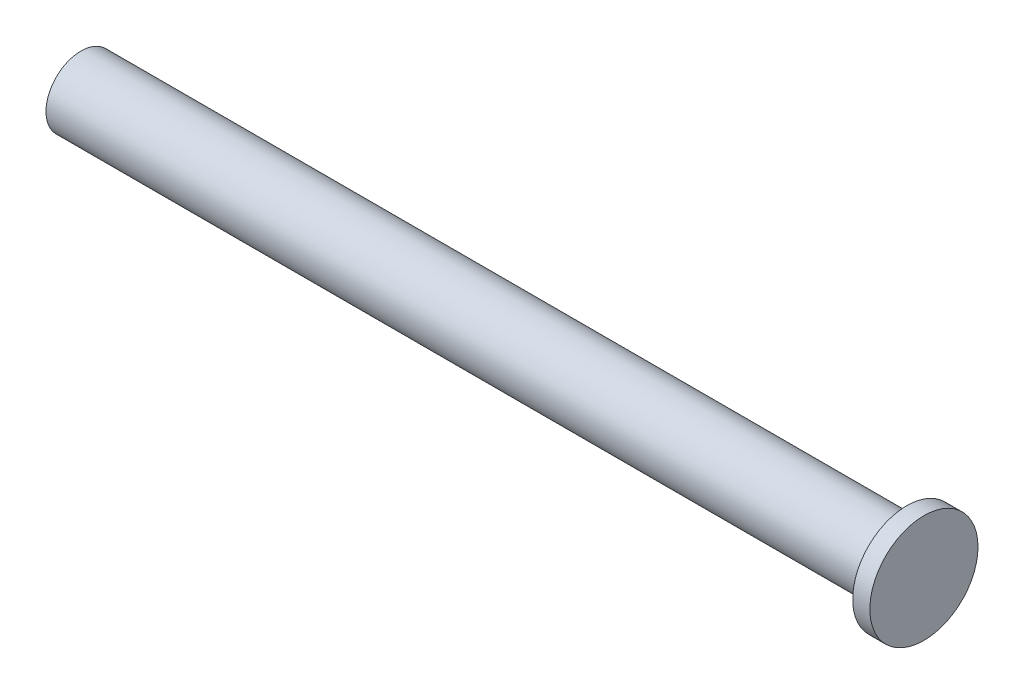
SolidWorks part; units mm, degrees
ref_plane "Front Plane" through (0, 0, 0) normal (0, 0, 1) x (1, 0, 0)
ref_plane "Top Plane" through (0, 0, 0) normal (0, 1, 0) x (1, 0, 0)
ref_plane "Right Plane" through (0, 0, 0) normal (1, 0, 0) x (0, 0, -1)
sketch "Sketch1" plane through (0, 0, 0) normal (1, 0, 0) x (0, 0, -1)
  circle A0 centre (0, 0) radius 3.2258
  dimension "D1" = 6.4516
extrude "Boss-Extrude1" add sketch "Sketch1" along normal mid plane 76.2
sketch "Sketch2" plane through (38.1, 0, 0) normal (1, 0, 0) x (0, 0, -1)
  circle A0 centre (0, 0) radius 4.9894
extrude "Boss-Extrude2" add sketch "Sketch2" along normal blind 1.5875
sketch "Sketch7" plane through (-38.1, 0, 0) normal (-1, 0, 0) x (0, 0, 1)
  circle A0 centre (0, 0) radius 1.905
  dimension "D1" = 3.81
extrude "Cut-Extrude1" cut sketch "Sketch7" against normal blind 12.7
thread "Thread1" pitch 0.7056 method cut profile "Thread Profile4" start angle 3, offset 0, length 12.7, pitch 0.7056, diameter 3.81
ref_plane "Plane4" through (-25.4, 0.0997, 1.9024) normal (0, -0.9986, 0.0523) x (0, 0.0523, 0.9986)
sketch "Thread Profile4" plane through (-25.4, 0.0997, 1.9024) normal (0, -0.9986, 0.0523) x (0, 0.0523, 0.9986)
  line L0 (0, 0) -> (0, 0.7056) construction
  line L1 (0, 0) -> (0.3819, 0.2205)
  line L2 (0.3819, 0.2205) -> (0.3819, 0.3087)
  line L3 (0.3819, 0.3087) -> (0, 0.5292)
  line L4 (0.3819, 0.2646) -> (0, 0.2646) construction
  line L11 (0, 0) -> (0, 0.5292)
  point P2 (0, 0)
  dimension "Pitch" = 0.7056
  dimension "Profile_Angle" = 60
  dimension "Profile_Land" = 0.0882
  dimension "Profile_Height" = 0.3819
ref_axis "Axis1" through (38.1, 0, 0) along (-1, 0, 0)
